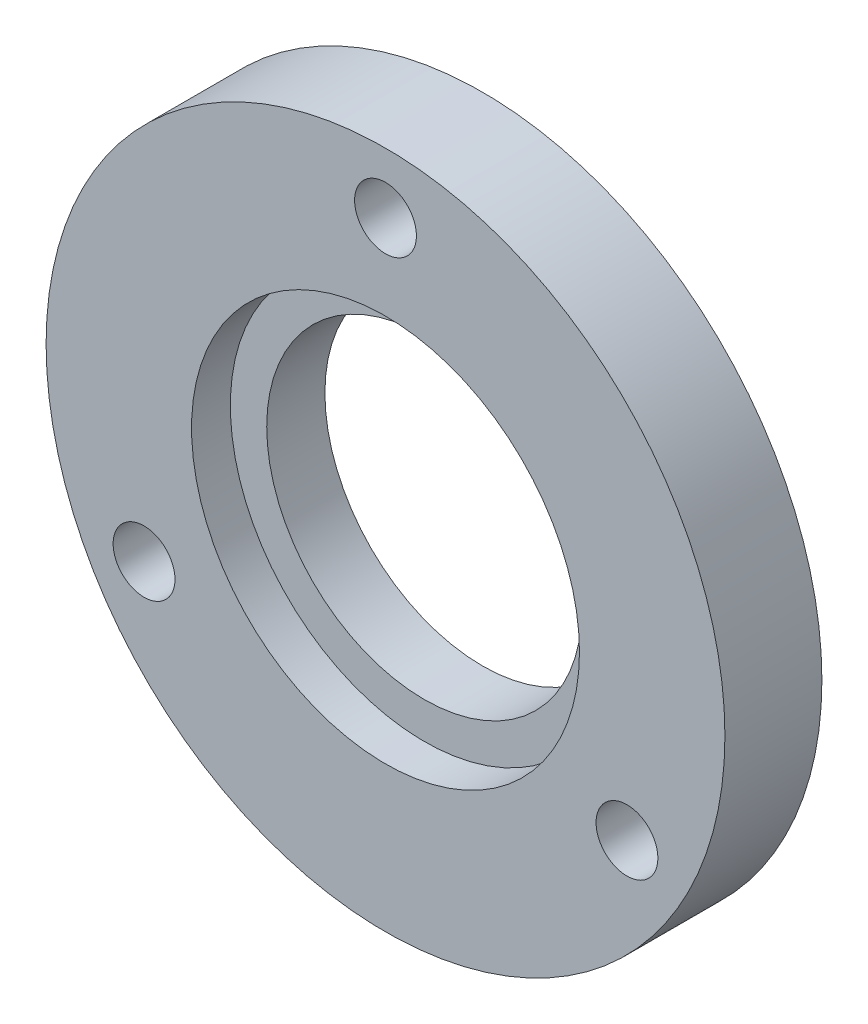
SolidWorks part; units mm, degrees
ref_plane "Front Plane" through (0, 0, 0) normal (0, 0, 1) x (1, 0, 0)
ref_plane "Top Plane" through (0, 0, 0) normal (0, 1, 0) x (1, 0, 0)
ref_plane "Right Plane" through (0, 0, 0) normal (1, 0, 0) x (0, 0, -1)
sketch "Sketch1" plane through (0, 0, 0) normal (0, 0, 1) x (1, 0, 0)
  line L0 (0, 23) -> (-19.9186, -11.5) construction
  line L1 (-19.9186, -11.5) -> (19.9186, -11.5) construction
  line L2 (19.9186, -11.5) -> (0, 23) construction
  circle A0 centre (0, 0) radius 13
  circle A1 centre (0, 0) radius 16 construction
  circle A3 centre (0, 0) radius 28
  circle A4 centre (0, 0) radius 23 construction
  circle A5 centre (0, 23) radius 2.55
  circle A6 centre (-19.9186, -11.5) radius 2.55
  circle A7 centre (19.9186, -11.5) radius 2.55
  circle A8 centre (0, 0) radius 16
  dimension "D1" = 26
  dimension "D2" = 32
  dimension "D4" = 56
  dimension "D5" = 46
  dimension "D6" = 5.1
  dimension "D7" = 5.1
  dimension "D8" = 5.1
extrude "Boss-Extrude1" add sketch "Sketch1" against normal blind 8 contours A8 A0 | A8 region at (-27.208, 0, 0) region at (-15.5475, 0, 0)
extrude "Boss-Extrude4" add sketch "Sketch1<7>" against normal blind 8 contours A3 A7 A6 A5 region at (-27.208, 0, 0)
sketch "Sketch1<7>" plane through (0, 0, 0) normal (0, 0, 1) x (1, 0, 0) same geometry as "Sketch1"
extrude "Cut-Extrude1" cut sketch "Sketch1<10>" against normal blind 3.2 contours A8 A0 region at (-15.5475, 0, 0)
sketch "Sketch1<10>" plane through (0, 0, 0) normal (0, 0, 1) x (1, 0, 0) same geometry as "Sketch1"
